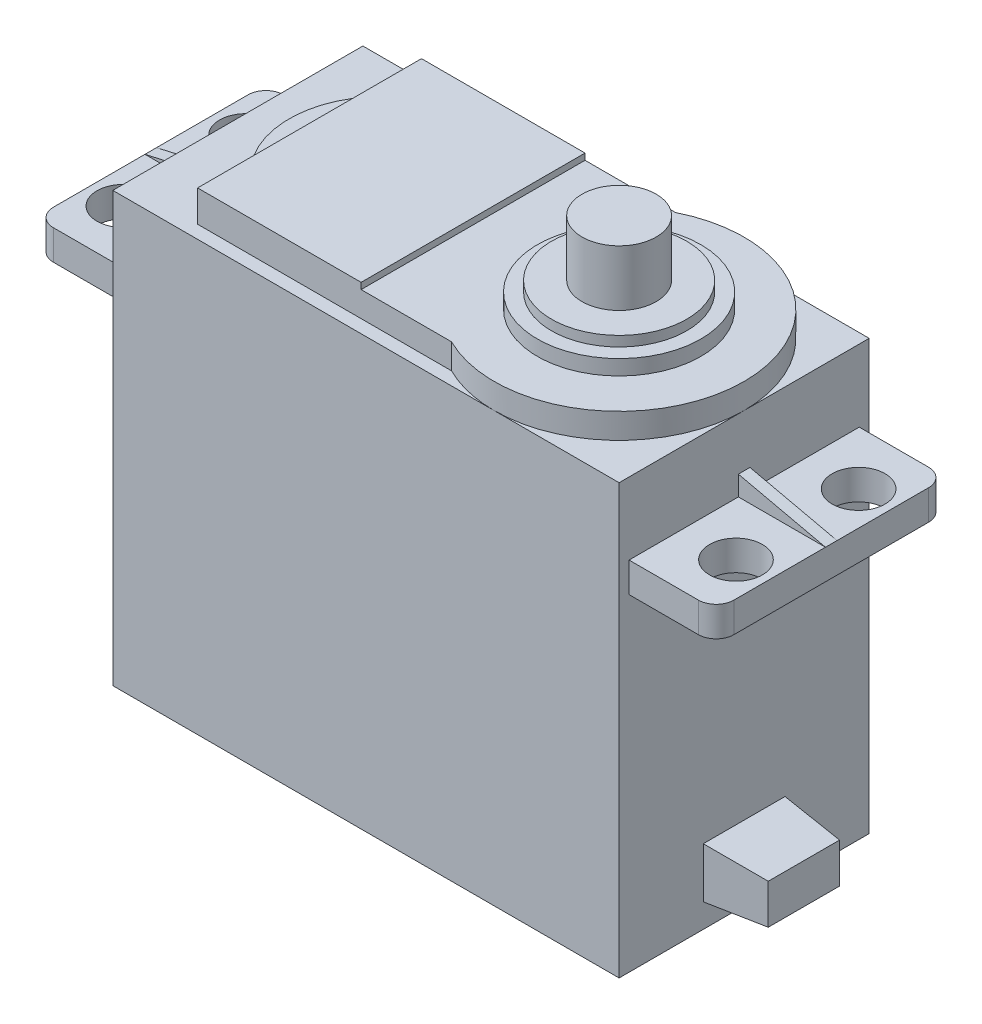
SolidWorks part; units mm, degrees
ref_plane "Front Plane" through (0, 0, 0) normal (0, 0, 1) x (1, 0, 0)
ref_plane "Top Plane" through (0, 0, 0) normal (0, 1, 0) x (1, 0, 0)
ref_plane "Right Plane" through (0, 0, 0) normal (1, 0, 0) x (0, 0, -1)
sketch "Sketch1" plane through (0, 0, 0) normal (0, 1, 0) x (1, 0, 0)
  line L0 (-27.05, 0) -> (27.05, 0) construction
  line L1 (-20.125, -9.94) -> (20.125, -9.94)
  line L2 (-20.125, -9.94) -> (-20.125, 9.94)
  line L3 (-20.125, 9.94) -> (20.125, 9.94)
  line L4 (20.125, -9.94) -> (20.125, 9.94)
  line L5 (-20.125, -9.94) -> (20.125, 9.94) construction
  line L6 (-20.125, 9.94) -> (20.125, -9.94) construction
  line L7 (-27.05, -9.15) -> (27.05, -9.15)
  line L8 (-27.05, -9.15) -> (-27.05, 9.15)
  line L9 (-27.05, 9.15) -> (27.05, 9.15)
  line L10 (27.05, -9.15) -> (27.05, 9.15)
  line L11 (-27.05, -9.15) -> (27.05, 9.15) construction
  line L12 (-27.05, 9.15) -> (27.05, -9.15) construction
  line L13 (0, 9.94) -> (0, -9.94) construction
  line L14 (-1.425, 8.9) -> (-1.425, -8.9)
  line L15 (5.7585, -8.9) -> (-14.425, -8.9)
  line L17 (5.7585, 8.9) -> (-14.425, 8.9)
  line L18 (-14.425, -8.9) -> (-14.425, 8.9)
  line L19 (5.7585, -8.9) -> (-14.425, 8.9) construction
  line L20 (5.7585, 8.9) -> (-14.425, -8.9) construction
  line L21 (-8.625, -8.9) -> (-8.625, 8.9) construction
  line L22 (-27.05, -0.46) -> (-20.125, -0.46)
  line L23 (-27.05, -0.46) -> (-27.05, 0.46)
  line L24 (-27.05, 0.46) -> (-20.125, 0.46)
  line L25 (-20.125, -0.46) -> (-20.125, 0.46)
  line L26 (-27.05, -0.46) -> (-20.125, 0.46) construction
  line L27 (-27.05, 0.46) -> (-20.125, -0.46) construction
  line L28 (27.05, -0.46) -> (20.125, -0.46)
  line L29 (27.05, -0.46) -> (27.05, 0.46)
  line L30 (27.05, 0.46) -> (20.125, 0.46)
  line L31 (20.125, -0.46) -> (20.125, 0.46)
  line L32 (27.05, -0.46) -> (20.125, 0.46) construction
  line L33 (27.05, 0.46) -> (20.125, -0.46) construction
  circle A1 centre (10.185, 0) radius 6.5
  arc A2 (5.7585, -8.9) -> (5.7585, 8.9) centre (10.185, 0) ccw
  circle A3 centre (-24.35, -4.875) radius 2.1
  circle A4 centre (-24.35, 4.875) radius 2.1
  circle A5 centre (24.35, -4.875) radius 2.1
  circle A6 centre (24.35, 4.875) radius 2.1
  arc A7 (-27.05, 7.7358) -> (-25.6358, 9.15) centre (-25.6358, 7.7358) cw
  arc A8 (-27.05, -7.7358) -> (-25.6358, -9.15) centre (-25.6358, -7.7358) ccw
  arc A9 (27.05, 7.7358) -> (25.6358, 9.15) centre (25.6358, 7.7358) ccw
  arc A10 (27.05, -7.7358) -> (25.6358, -9.15) centre (25.6358, -7.7358) cw
  circle A11 centre (10.185, 0) radius 5.375
  circle A12 centre (10.185, 0) radius 2.95
  arc A14 (-14.425, 4.6278) -> (-14.425, -4.6278) centre (-8.625, 0) ccw
  point P0 (0, 0)
  point P6 (0, 0)
  point P18 (-4.3332, 0)
  point P38 (-23.5875, 0)
  point P39 (-26.6358, 8.7358)
  point P53 (23.5875, 0)
  point P62 (0, 0)
  point P63 (0, 0)
  dimension "D7" = 4.2
  dimension "D12" = 13
  dimension "D13" = 10.75
  dimension "D14" = 5.9
  dimension "D17" = 7.42
  dimension "D1" = 40.25
  dimension "D2" = 19.88
  dimension "D3" = 18.3
  dimension "D4" = 54.1
  dimension "D5" = 17.8
  dimension "D6" = 5.7
  dimension "D8" = 9.75
  dimension "D9" = 48.7
  dimension "D10" = 13
  dimension "D11" = 1
  dimension "D15" = 0.92
  dimension "D16" = 5.8
extrude "Boss-Extrude1" add sketch "Sketch1" along normal blind 2.38 contours L8 A8 L7 L2 L22 A3 | A7 L8 L24 L2 L9 A4 | A2 L9 L2 L7 L15 L18 L17 | L18 L15 L14 L17 | L7 A2 L9 L17 L14 L15 A1 | A1 A11 | A11 A12 | A12 | A2 L31 L4 L9 | L10 A9 L9 L4 L30 A6 | L10 L30 L31 L4 L28 | A10 L10 L28 L4 L7 A5 | A2 L7 L4 | A2 L1 L4 L7 | A2 L7 | A2 L7 L2 L1 | A2 L9 L4 L3 | L9 A2 | A2 L3 L2 L9 | L24 L8 L22 L2 region at (-6.2601, 0, 9.5523) region at (16.4034, 0, 9.5727) region at (10.185, 0, 9.4671) region at (-22.8804, 0, 9.0389) region at (-16.2088, 0, 0) region at (6.1464, 0, 8.7723) region at (18.4687, 0, 7.0236) region at (-23.5875, 0, 0) region at (20.2361, 0, 4.805) region at (23.5875, 0, 0) region at (18.4687, 0, -7.0236) region at (-23.5875, 0, -0.5711) region at (-7.925, 0, 0) region at (20.2361, 0, -4.805) region at (16.4034, 0, -9.5727) region at (10.185, 0, -9.4671) region at (-6.2601, 0, -9.5523) region at (3.8688, 0, 0) region at (4.962, 0, 0) region at (10.185, 0, 0)
extrude "Boss-Extrude2" add sketch "Sketch1<3>" along normal blind 5.72 from surface contours L2 L3 L4 L1 | L22 L25 L24 L23 | L28 L31 L30 L29 starting at face at (0, 2.38, 0)
sketch "Sketch1<3>" plane through (0, 0, 0) normal (0, 1, 0) x (1, 0, 0) same geometry as "Sketch1"
extrude "Boss-Extrude3" add sketch "Sketch1<4>" along normal blind 2 from surface contours L18 A14 | A2 L17 L18 L15 region at (-15.0795, 0, 0) starting at face at (0, 8.1, 0)
sketch "Sketch1<4>" plane through (0, 0, 0) normal (0, 1, 0) x (1, 0, 0) same geometry as "Sketch1"
extrude "Boss-Extrude4" add sketch "Sketch1<5>" along normal blind 0.5 from surface contours L18 L15 L14 L17 region at (-7.925, 0, 0) starting at face at (-5.5727, 10.1, 0)
sketch "Sketch1<5>" plane through (0, 0, 0) normal (0, 1, 0) x (1, 0, 0) same geometry as "Sketch1"
extrude "Boss-Extrude5" add sketch "Sketch1<6>" along normal blind 1.2 from surface contours A1 starting at face at (5.7584, 10.1, 0)
sketch "Sketch1<6>" plane through (0, 0, 0) normal (0, 1, 0) x (1, 0, 0) same geometry as "Sketch1"
extrude "Boss-Extrude6" add sketch "Sketch1<8>" along normal blind 2 from surface contours A11 starting at face at (10.185, 10.1, -6.5)
sketch "Sketch1<8>" plane through (0, 0, 0) normal (0, 1, 0) x (1, 0, 0) same geometry as "Sketch1"
extrude "Boss-Extrude7" add sketch "Sketch1<9>" along normal blind 6.45 from surface contours A12 region at (10.185, 0, 0) starting at face at (10.185, 10.1, -6.5)
sketch "Sketch1<9>" plane through (0, 0, 0) normal (0, 1, 0) x (1, 0, 0) same geometry as "Sketch1"
extrude "Boss-Extrude8" add sketch "Sketch1<10>" against normal blind 28 contours L4 L3 L2 L1
sketch "Sketch1<10>" plane through (0, 0, 0) normal (0, 1, 0) x (1, 0, 0) same geometry as "Sketch1"
chamfer "Chamfer1" distance 2 angle 45 4 edges at (20.125, -28, 0) (0, -28, -9.94) (-20.125, -28, 0) (0, -28, 9.94)
sketch "Sketch2" plane through (20.125, 0, 0) normal (1, 0, 0) x (0, 0, -1)
  line L0 (0, -26) -> (0, 0) construction
  line L1 (-9.94, -26) -> (9.94, -26) construction
  line L2 (7.94, -28) -> (-7.94, -28) construction
  line L3 (-3.25, -24.1) -> (3.25, -24.1)
  line L4 (-3.25, -24.1) -> (-3.25, -20.1)
  line L5 (-3.25, -20.1) -> (3.25, -20.1)
  line L6 (3.25, -24.1) -> (3.25, -20.1)
  line L7 (-3.25, -24.1) -> (3.25, -20.1) construction
  line L8 (-3.25, -20.1) -> (3.25, -24.1) construction
  point P5 (0, -22.1)
  dimension "D1" = 4
  dimension "D2" = 6.5
  dimension "D3" = 7.9
extrude "Boss-Extrude9" add sketch "Sketch2" along normal blind 4.75 draft 5
sketch "Sketch3" plane through (0, 0, -9.94) normal (0, 0, -1) x (-1, 0, 0)
  line L0 (-27.05, 2.38) -> (-20.125, 2.38)
  line L1 (-20.125, 2.38) -> (-20.125, 3.95)
  line L2 (-20.125, 8.1) -> (-20.125, 2.38) construction
  line L3 (-20.125, 3.95) -> (-27.05, 2.38)
  line L4 (20.125, 2.38) -> (27.05, 2.38)
  line L5 (27.05, 2.38) -> (20.125, 3.95)
  line L6 (20.125, 8.1) -> (20.125, -26) construction
  line L7 (20.125, 3.95) -> (20.125, 2.38)
  line L8 (25.6358, 0) -> (20.125, 0) construction
  line L9 (-27.05, 2.38) -> (-27.05, 8.1)
  line L10 (-27.05, 8.1) -> (-20.125, 8.1)
  line L11 (-20.125, 8.1) -> (-20.125, 3.95)
  line L12 (20.125, 3.95) -> (20.125, 8.1)
  line L13 (20.125, 8.1) -> (27.05, 8.1)
  line L14 (27.05, 8.1) -> (27.05, 2.38)
  line M7 (-20.125, 8.1) -> (-20.125, -26)
  line M9 (20.125, -26) -> (20.125, 8.1)
  dimension "D1" = 3.95
extrude "Cut-Extrude1" cut sketch "Sketch3" against normal through all contours L10 L9 L3 M7 | L14 L13 L5 M9 region at (23.7711, 5.6117, -9.94) region at (-23.7711, 5.6117, -9.94)
